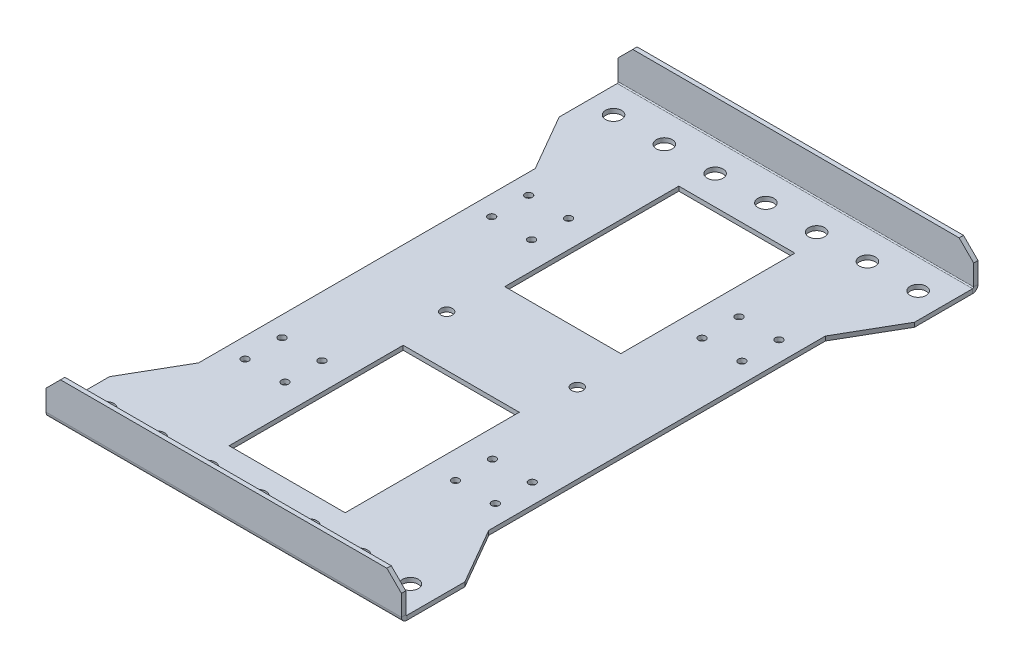
SolidWorks part; units mm, degrees
note: The reader was unsure of these and kept them because the rebuilt part matched: flange length of "Brida de arista1".
material "1023 Chapa de acero al carbono (SS)"
ref_plane "Alzado" through (0, 0, 0) normal (0, 0, 1) x (1, 0, 0)
ref_plane "Planta" through (0, 0, 0) normal (0, 1, 0) x (1, 0, 0)
ref_plane "Vista lateral" through (0, 0, 0) normal (1, 0, 0) x (0, 0, -1)
sketch "Croquis1" plane through (0, 0, 0) normal (0, 1, 0) x (1, 0, 0)
  line L1 (-122.5, -195) -> (122.5, -195)
  line L2 (-122.5, -195) -> (-122.5, 195)
  line L3 (-122.5, 195) -> (122.5, 195)
  line L4 (122.5, -195) -> (122.5, 195)
  line L5 (-122.5, -195) -> (122.5, 195) construction
  line L6 (-122.5, 195) -> (122.5, -195) construction
  point P0 (0, 0)
  dimension "D1" = 245
  dimension "D2" = 390
base flange "Brida base1" sketch "Croquis1" thickness 3 reverse thickness direction no parameters "D1"=0.7366
edge flange "Brida de arista1" sketch "Croquis10" flange profiles "Croquis10", "Croquis11" flange angle 90 flange length 25 flange position bend outside bend radius 0.7366 thickness 3 relief rectangular parameters "D6"=10, "D8"=1
sketch "Croquis10" plane through (0, 0, -195) normal (0, 0, -1) x (-1, 0, 0)
  line L2 (-122.5, 0) -> (-122.5, 25)
  line L3 (-122.5, 25) -> (122.5, 25)
  line L4 (122.5, 25) -> (122.5, 0)
  line L5 (-122.5, 0) -> (122.5, 0) construction
  line L6 (-122.5, 0) -> (122.5, 0)
sketch "Croquis11" plane through (0, 0, 195) normal (0, 0, 1) x (1, 0, 0)
  line L1 (-122.5, 0) -> (122.5, 0) construction
  line L2 (122.5, 0) -> (122.5, 25)
  line L3 (122.5, 25) -> (-122.5, 25)
  line L4 (-122.5, 25) -> (-122.5, 0)
  line L5 (-122.5, 0) -> (122.5, 0)
bend "Pliegue de arista1" bend radius 0.7366 bend angle 90 parameters "D5"=1
bend "Pliegue de arista2" bend radius 0.7366 bend angle 90 parameters "D5"=2
sketch "Croquis12" plane through (0, 0, 0) normal (0, 1, 0) x (1, 0, 0)
  line L0 (122.5, 155) -> (-122.5, 155) construction
  line L1 (-70, 195) -> (-70, -195) construction
  line L2 (70, 195) -> (70, -195) construction
  line L3 (-100, 195) -> (-100, -195) construction
  line L4 (122.5, -195) -> (122.5, 195)
  line L5 (122.5, 195) -> (-122.5, 195)
  line L6 (-122.5, 195) -> (-122.5, -195)
  line L7 (-122.5, -195) -> (122.5, -195)
  line L8 (122.5, -195) -> (122.5, 195)
  line L9 (122.5, 195) -> (-122.5, 195)
  line L10 (-122.5, 195) -> (-122.5, -195)
  line L11 (-122.5, -195) -> (122.5, -195)
  line L12 (40, 195) -> (40, -195) construction
  line L13 (-40, 195) -> (-40, -195) construction
  line L14 (100, 195) -> (100, -195) construction
  line L15 (-122.5, -155) -> (122.5, -155) construction
  line L16 (-40, 0) -> (40, 0) construction
  line L17 (-40, -35) -> (40, -35)
  line L18 (-40, 35) -> (40, 35)
  line L19 (-122.5, 155) -> (-100, 116.0289)
  line L20 (-100, 116.0289) -> (-100, 0)
  line L21 (-40, 35) -> (-40, 155)
  line L22 (-40, 155) -> (40, 155)
  line L23 (40, 155) -> (40, 35)
  line L24 (100, 0) -> (100, 116.0289)
  line L25 (100, 116.0289) -> (122.5, 155)
  line L26 (-40, -35) -> (-40, -155)
  line L27 (-40, -155) -> (40, -155)
  line L28 (40, -155) -> (40, -35)
  line L29 (-100, 0) -> (-100, -116.0289)
  line L30 (-100, -116.0289) -> (-122.5, -155)
  line L31 (100, 0) -> (100, -116.0289)
  line L32 (100, -116.0289) -> (122.5, -155)
  dimension "D3" = 70
  dimension "D4" = 70
  dimension "D8" = 35
  dimension "D10" = 30
  dimension "D11" = 30
  dimension "D1" = 0
  dimension "D2" = 40
  dimension "D5" = 30
  dimension "D6" = 30
  dimension "D7" = 40
  dimension "D9" = 35
extrude "Cortar-Extruir1" cut sketch "Croquis12" against normal up to surface (3 mm away) contours L30 L29 L20 L19 L10 | L27 L28 L17 L26 | L31 L32 L8 L25 L24 | L23 L22 L21 L18 normal cut yes up to face at (0, -3, 0)
sketch "Croquis13" plane through (0, 0, 0) normal (0, 1, 0) x (1, 0, 0)
  line L0 (0, 0) -> (0, 85) construction
  line L1 (-72.5, -85) -> (72.5, -85) construction
  line L2 (-72.5, -85) -> (-72.5, 85) construction
  line L3 (-72.5, 85) -> (72.5, 85) construction
  line L4 (72.5, -85) -> (72.5, 85) construction
  line L5 (-72.5, -85) -> (72.5, 85) construction
  line L6 (-72.5, 85) -> (72.5, -85) construction
  line L7 (-86.25, 97.75) -> (-58.75, 97.75) construction
  line L8 (-86.25, 97.75) -> (-86.25, 72.25) construction
  line L9 (-86.25, 72.25) -> (-58.75, 72.25) construction
  line L10 (-58.75, 97.75) -> (-58.75, 72.25) construction
  line L11 (-86.25, 97.75) -> (-58.75, 72.25) construction
  line L12 (-86.25, 72.25) -> (-58.75, 97.75) construction
  line L13 (0, 0) -> (-72.5, 0) construction
  line L14 (86.25, 97.75) -> (58.75, 72.25) construction
  line L15 (86.25, 72.25) -> (58.75, 97.75) construction
  line L16 (86.25, 72.25) -> (58.75, 72.25) construction
  line L17 (58.75, 97.75) -> (58.75, 72.25) construction
  line L18 (86.25, 97.75) -> (58.75, 97.75) construction
  line L19 (86.25, 97.75) -> (86.25, 72.25) construction
  circle A0 centre (-86.25, 97.75) radius 2.5
  circle A1 centre (-58.75, 97.75) radius 2.5
  circle A2 centre (-86.25, 72.25) radius 2.5
  circle A3 centre (-58.75, 72.25) radius 2.5
  circle A4 centre (86.25, 72.25) radius 2.5
  circle A5 centre (58.75, 72.25) radius 2.5
  circle A6 centre (58.75, 97.75) radius 2.5
  circle A7 centre (86.25, 97.75) radius 2.5
  circle A8 centre (86.25, -72.25) radius 2.5
  circle A9 centre (58.75, -72.25) radius 2.5
  circle A10 centre (86.25, -97.75) radius 2.5
  circle A11 centre (58.75, -97.75) radius 2.5
  circle A12 centre (-58.75, -72.25) radius 2.5
  circle A13 centre (-58.75, -97.75) radius 2.5
  circle A14 centre (-86.25, -97.75) radius 2.5
  circle A15 centre (-86.25, -72.25) radius 2.5
  point P0 (0, 0)
  dimension "D5" = 5
  dimension "D1" = 145
  dimension "D2" = 170
  dimension "D3" = 25.5
  dimension "D4" = 27.5
extrude "Cortar-Extruir2" cut sketch "Croquis13" against normal up to surface (3 mm away) normal cut yes up to face at (0, -3, -95)
chamfer "Chaflán1" distance 10 angle 45 4 edges at (-122.5, 25, 197.2366) (122.5, 25, 197.2366) (122.5, 25, -197.2366) (-122.5, 25, -197.2366)
sketch "Croquis14" plane through (0, 0, 0) normal (0, 1, 0) x (1, 0, 0)
  line L0 (-122.5, 175) -> (122.5, 175) construction
  line L1 (-122.5, 195) -> (-122.5, 155) construction
  line L2 (122.5, 155) -> (122.5, 195) construction
  line L3 (122.5, 195) -> (-122.5, 195) construction
  line L4 (-100, 0) -> (100, 0) construction
  line L5 (-100, 116.0289) -> (-100, -116.0289) construction
  line L6 (100, 116.0289) -> (100, -116.0289) construction
  line L7 (-122.5, -175) -> (122.5, -175) construction
  circle A0 centre (-105, 175) radius 5.5
  circle A1 centre (-70, 175) radius 5.5
  circle A2 centre (-35, 175) radius 5.5
  circle A3 centre (0, 175) radius 5.5
  circle A4 centre (35, 175) radius 5.5
  circle A5 centre (70, 175) radius 5.5
  circle A6 centre (105, 175) radius 5.5
  circle A7 centre (105, -175) radius 5.5
  circle A8 centre (70, -175) radius 5.5
  circle A9 centre (35, -175) radius 5.5
  circle A10 centre (0, -175) radius 5.5
  circle A11 centre (-35, -175) radius 5.5
  circle A12 centre (-70, -175) radius 5.5
  circle A13 centre (-105, -175) radius 5.5
  dimension "D2" = 17.5
  dimension "D3" = 11
  dimension "D1" = 20
  dimension "D4" = 7
extrude "Cortar-Extruir3" cut sketch "Croquis14" against normal up to surface (3 mm away) normal cut yes up to face at (-58.75, -3, -100.25)
sketch "Croquis15" plane through (0, -3, 0) normal (0, -1, 0) x (1, 0, 0)
  circle A0 centre (45, 0) radius 4 construction
  circle A1 centre (45, 0) radius 4
  circle A2 centre (-45, 0) radius 4 construction
  circle A3 centre (-45, 0) radius 4
extrude "Cortar-Extruir4" cut sketch "Croquis15" against normal up to surface (3 mm away) normal cut yes up to face at (-70, 0, -169.5)
sketch "Líneas de pliegue1" [suppressed] plane through (0, 0, 0) normal (0, 1, 0) x (1, 0, 0)
sketch "Cuadro delimitador1" [suppressed] plane through (0, 0, 0) normal (0, 1, 0) x (1, 0, 0)
sheet metal parameters "Chapa metálica1" thickness 3 parameters "D1"=0.7366
flat pattern "Chapa desplegada1" [suppressed]
sketch "Líneas de pliegue2" plane through (0, 0, 0) normal (0, 1, 0) x (1, 0, 0)
sketch3d "Cuadro delimitador2" [suppressed]
  line L0 (122.5, -195, 0) -> (122.5, 195, 0) construction
  line L1 (-122.5, -195, 0) -> (-122.5, 195, 0) construction
  line L2 (122.5, -195, 0) -> (-122.5, -195, 0) construction
  line L3 (122.5, 195, 0) -> (-122.5, 195, 0) construction
sheet metal parameters "Chapa metálica2" thickness 3 parameters "D1"=0.7366
flat pattern "Chapa desplegada1"
sketch "Líneas de pliegue2" plane through (0, 0, 0) normal (0, 1, 0) x (1, 0, 0)
  line L0 (-122.5, -196.7566) -> (122.5, -196.7566) construction
  line L1 (122.5, 196.7566) -> (-122.5, 196.7566) construction
  line L2 (-122.5, -196.7566) -> (122.5, -196.7566) construction
  line L3 (122.5, 196.7566) -> (-122.5, 196.7566) construction
sketch3d "Cuadro delimitador2" [suppressed]
  line L0 (-122.5, -222.7766, 0) -> (-122.5, 222.7766, 0) construction
  line L1 (122.5, -222.7766, 0) -> (122.5, 222.7766, 0) construction
  line L2 (-122.5, -222.7766, 0) -> (122.5, -222.7766, 0) construction
  line L3 (-122.5, 222.7766, 0) -> (122.5, 222.7766, 0) construction
bend of the flat pattern "Aplanar-<Pliegue de arista1>1"
bend of the flat pattern "Aplanar-<Pliegue de arista2>1"
sheet metal parameters "Chapa metálica3" thickness 3 parameters "D1"=0.7366
flat pattern "Chapa desplegada1"
sketch "Líneas de pliegue2" plane through (0, 0, 0) normal (0, 1, 0) x (1, 0, 0)
  line L0 (-122.5, -196.7566) -> (122.5, -196.7566) construction
  line L1 (122.5, 196.7566) -> (-122.5, 196.7566) construction
  line L2 (-122.5, -196.7566) -> (122.5, -196.7566) construction
  line L3 (122.5, 196.7566) -> (-122.5, 196.7566) construction
sketch3d "Cuadro delimitador2" [suppressed]
  line L0 (-122.5, -222.7766, 0) -> (-122.5, 222.7766, 0) construction
  line L1 (122.5, -222.7766, 0) -> (122.5, 222.7766, 0) construction
  line L2 (-122.5, -222.7766, 0) -> (122.5, -222.7766, 0) construction
  line L3 (-122.5, 222.7766, 0) -> (122.5, 222.7766, 0) construction
bend of the flat pattern "Aplanar-<Pliegue de arista1>1"
bend of the flat pattern "Aplanar-<Pliegue de arista2>1"
sheet metal parameters "Chapa metálica4" thickness 3 parameters "D1"=0.7366
flat pattern "Chapa desplegada1"
sketch "Líneas de pliegue2" plane through (0, 0, 0) normal (0, 1, 0) x (1, 0, 0)
  line L0 (-122.5, -196.7566) -> (122.5, -196.7566) construction
  line L1 (122.5, 196.7566) -> (-122.5, 196.7566) construction
  line L2 (-122.5, -196.7566) -> (122.5, -196.7566) construction
  line L3 (122.5, 196.7566) -> (-122.5, 196.7566) construction
sketch3d "Cuadro delimitador2" [suppressed]
  line L0 (-122.5, -222.7766, 0) -> (-122.5, 222.7766, 0) construction
  line L1 (122.5, -222.7766, 0) -> (122.5, 222.7766, 0) construction
  line L2 (-122.5, -222.7766, 0) -> (122.5, -222.7766, 0) construction
  line L3 (-122.5, 222.7766, 0) -> (122.5, 222.7766, 0) construction
bend of the flat pattern "Aplanar-<Pliegue de arista1>1"
bend of the flat pattern "Aplanar-<Pliegue de arista2>1"
sheet metal parameters "Chapa metálica5" thickness 3 parameters "D1"=0.7366
flat pattern "Chapa desplegada1"
sketch "Líneas de pliegue2" plane through (0, 0, 0) normal (0, 1, 0) x (1, 0, 0)
  line L0 (-122.5, -196.7566) -> (122.5, -196.7566) construction
  line L1 (122.5, 196.7566) -> (-122.5, 196.7566) construction
  line L2 (-122.5, -196.7566) -> (122.5, -196.7566) construction
  line L3 (122.5, 196.7566) -> (-122.5, 196.7566) construction
sketch3d "Cuadro delimitador2" [suppressed]
  line L0 (-122.5, -222.7766, 0) -> (-122.5, 222.7766, 0) construction
  line L1 (122.5, -222.7766, 0) -> (122.5, 222.7766, 0) construction
  line L2 (-122.5, -222.7766, 0) -> (122.5, -222.7766, 0) construction
  line L3 (-122.5, 222.7766, 0) -> (122.5, 222.7766, 0) construction
bend of the flat pattern "Aplanar-<Pliegue de arista1>1"
bend of the flat pattern "Aplanar-<Pliegue de arista2>1"
sheet metal parameters "Chapa metálica6" thickness 3 parameters "D1"=0.7366
flat pattern "Chapa desplegada1"
sketch "Líneas de pliegue2" plane through (0, 0, 0) normal (0, 1, 0) x (1, 0, 0)
  line L0 (-122.5, -196.7566) -> (122.5, -196.7566) construction
  line L1 (122.5, 196.7566) -> (-122.5, 196.7566) construction
  line L2 (-122.5, -196.7566) -> (122.5, -196.7566) construction
  line L3 (122.5, 196.7566) -> (-122.5, 196.7566) construction
sketch3d "Cuadro delimitador2" [suppressed]
  line L0 (-122.5, -222.7766, 0) -> (-122.5, 222.7766, 0) construction
  line L1 (122.5, -222.7766, 0) -> (122.5, 222.7766, 0) construction
  line L2 (-122.5, -222.7766, 0) -> (122.5, -222.7766, 0) construction
  line L3 (-122.5, 222.7766, 0) -> (122.5, 222.7766, 0) construction
bend of the flat pattern "Aplanar-<Pliegue de arista1>1"
bend of the flat pattern "Aplanar-<Pliegue de arista2>1"
